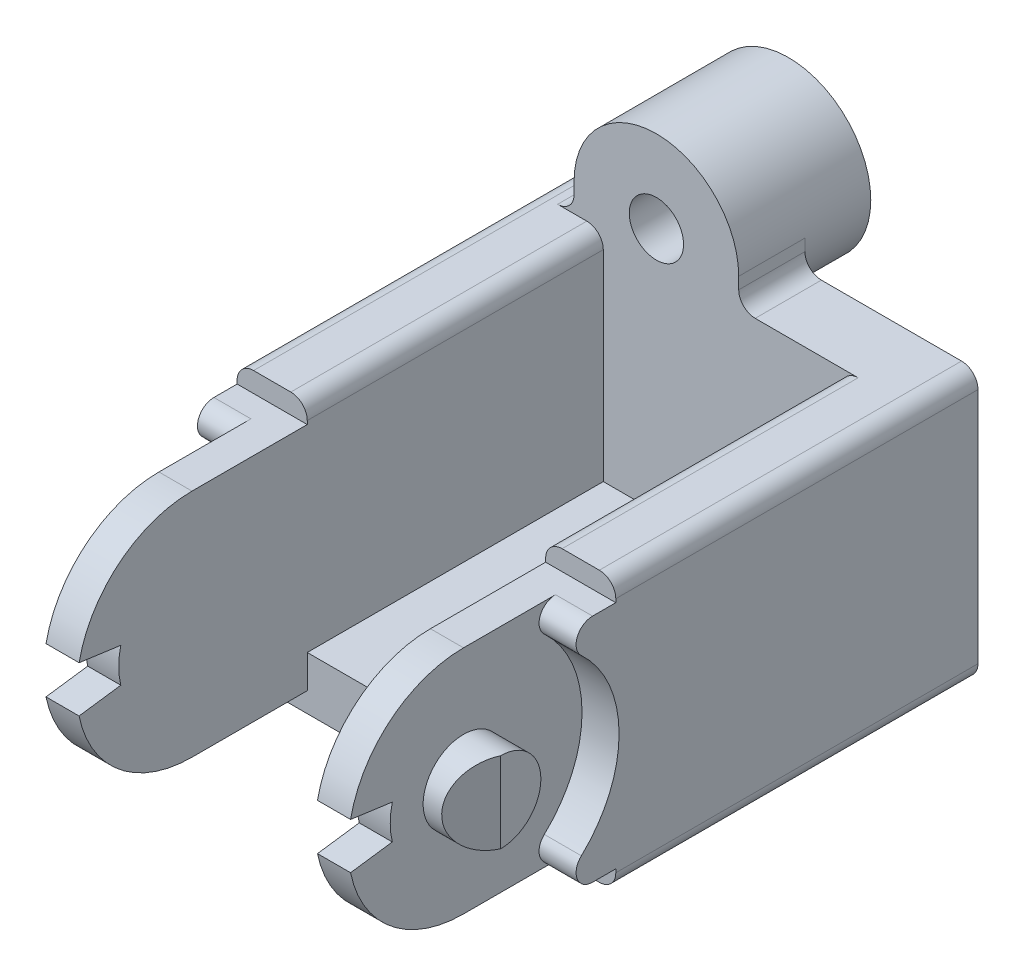
SolidWorks part; units mm, degrees
ref_plane "Front Plane" through (0, 0, 0) normal (0, 0, 1) x (1, 0, 0)
ref_plane "Top Plane" through (0, 0, 0) normal (0, 1, 0) x (1, 0, 0)
ref_plane "Right Plane" through (0, 0, 0) normal (1, 0, 0) x (0, 0, -1)
sketch "Sketch1" plane through (0, 0, 0) normal (0, 0, 1) x (1, 0, 0)
  line L0 (6, -1.7119) -> (14.5132, -1.7119)
  line L1 (-6.4868, -1.7119) -> (-6, -1.7119)
  line L2 (14.5132, -18.1319) -> (-6.4868, -18.1319)
  line L15 (15.5132, -2.7119) -> (15.5132, -17.1319)
  line L16 (-7.4868, -2.7119) -> (-7.4868, -17.1319)
  line L18 (-5, 0) -> (-5, -0.7119)
  line L20 (5, 0) -> (5, -0.7119)
  circle A3 centre (0, 0) radius 1.65
  arc A4 (14.5132, -18.1319) -> (15.5132, -17.1319) centre (14.5132, -17.1319) ccw
  arc A5 (14.5132, -1.7119) -> (15.5132, -2.7119) centre (14.5132, -2.7119) cw
  arc A6 (-6.4868, -1.7119) -> (-7.4868, -2.7119) centre (-6.4868, -2.7119) ccw
  arc A7 (-6.4868, -18.1319) -> (-7.4868, -17.1319) centre (-6.4868, -17.1319) cw
  arc A9 (5, 0) -> (-5, 0) centre (0, 0) ccw
  arc A10 (6, -1.7119) -> (5, -0.7119) centre (6, -0.7119) cw
  arc A11 (-5, -0.7119) -> (-6, -1.7119) centre (-6, -0.7119) cw
  point P39 (0, 0)
extrude "Boss-Extrude1" add sketch "Sketch1" along normal blind 40
sketch "Sketch2" plane through (0, 0, 40) normal (0, 0, 1) x (1, 0, 0)
  line L0 (5, 0) -> (5, -0.7119)
  line L2 (-5, -0.7119) -> (-5, 0)
  line L3 (-3.2268, -14.9119) -> (-3.2268, -2.7119)
  line L4 (-4.2268, -1.7119) -> (-6, -1.7119)
  line L5 (-3.2268, -14.9119) -> (11.2532, -14.9119)
  line L6 (11.2532, -14.9119) -> (11.2532, -2.7119)
  line L9 (12.2532, -1.7119) -> (6, -1.7119)
  arc A1 (-6, -1.7119) -> (-5, -0.7119) centre (-6, -0.7119) ccw
  arc A2 (5, -0.7119) -> (6, -1.7119) centre (6, -0.7119) ccw
  arc A3 (11.2532, -2.7119) -> (12.2532, -1.7119) centre (12.2532, -2.7119) cw
  arc A4 (-3.2268, -2.7119) -> (-4.2268, -1.7119) centre (-4.2268, -2.7119) ccw
  arc A5 (5, 0) -> (-5, 0) centre (0, 0) ccw
extrude "Cut-Extrude1" cut sketch "Sketch2" against normal offset from surface (31.98 mm away) 8.02 up to face at (2.2932, -5.6884, 0)
sketch "Sketch3" plane through (0, 0, 0) normal (0, 0, -1) x (-1, 0, 0)
  line L0 (-5, 0) -> (-5, -0.7119)
  line L2 (5, 0) -> (5, -0.7119)
  line L3 (-14.5132, -1.7119) -> (-6, -1.7119)
  line L4 (-15.5132, -2.7119) -> (-15.5132, -17.1319)
  line L6 (-14.5132, -18.1319) -> (6.4868, -18.1319)
  line L8 (7.4868, -17.1319) -> (7.4868, -2.7119)
  line L10 (6.4868, -1.7119) -> (6, -1.7119)
  arc A0 (-5, 0) -> (5, 0) centre (0, 0) ccw
  arc A1 (5, -0.7119) -> (6, -1.7119) centre (6, -0.7119) ccw
  arc A2 (-6, -1.7119) -> (-5, -0.7119) centre (-6, -0.7119) ccw
  arc A3 (7.4868, -2.7119) -> (6.4868, -1.7119) centre (6.4868, -2.7119) ccw
  arc A4 (-14.5132, -1.7119) -> (-15.5132, -2.7119) centre (-14.5132, -2.7119) ccw
  arc A5 (-15.5132, -17.1319) -> (-14.5132, -18.1319) centre (-14.5132, -17.1319) ccw
  arc A6 (6.4868, -18.1319) -> (7.4868, -17.1319) centre (6.4868, -17.1319) ccw
  circle A7 centre (0, 0) radius 3.3
extrude "Cut-Extrude2" cut sketch "Sketch3" against normal blind 4
sketch "Sketch4" plane through (0, 0, 40) normal (0, 0, 1) x (1, 0, 0)
  line L1 (-3.2268, -16.9219) -> (-3.2268, -2.9219)
  line L3 (11.2532, -16.9219) -> (11.2532, -2.9219)
  line L5 (-7.4868, -1.7119) -> (15.5132, -1.7119)
  line L6 (-7.4868, -1.7119) -> (-7.4868, -2.9219)
  line L7 (-7.4868, -2.9219) -> (-3.2268, -2.9219)
  line L8 (15.5132, -1.7119) -> (15.5132, -2.9219)
  line L9 (11.2532, -2.9219) -> (15.5132, -2.9219)
  line L10 (-7.4868, -18.1319) -> (15.5132, -18.1319)
  line L11 (-7.4868, -18.1319) -> (-7.4868, -16.9219)
  line L12 (-7.4868, -16.9219) -> (-3.2268, -16.9219)
  line L13 (15.5132, -18.1319) -> (15.5132, -16.9219)
  line L14 (11.2532, -16.9219) -> (15.5132, -16.9219)
extrude "Cut-Extrude3" cut sketch "Sketch4" against normal blind 14
sketch "Sketch5" plane through (15.5132, 0, 0) normal (1, 0, 0) x (0, 0, -1)
  line L0 (-39.8586, -8.5219) -> (-37.3243, -8.8719)
  line L1 (-39.8586, -11.3219) -> (-37.3243, -10.9719)
  line L2 (-33, -2.9219) -> (-40, -2.9219)
  line L3 (-40, -2.9219) -> (-40, -16.9219)
  line L4 (-40, -16.9219) -> (-33, -16.9219)
  arc A0 (-39.8586, -11.3219) -> (-33, -16.9219) centre (-33, -9.9219) ccw
  arc A1 (-37.3243, -8.8719) -> (-37.3243, -10.9719) centre (-33, -9.9219) ccw
  arc A2 (-33, -2.9219) -> (-39.8586, -8.5219) centre (-33, -9.9219) ccw
extrude "Cut-Extrude4" cut sketch "Sketch5" against normal up to surface (23 mm away) up to face at (-7.4868, -9.9219, 24)
sketch "Sketch6" plane through (15.5132, 0, 0) normal (1, 0, 0) x (0, 0, -1)
  line L0 (-27.4107, -2.9219) -> (-31.3148, -2.9219)
  line L1 (-27.4107, -16.9219) -> (-31.3148, -16.9219)
  circle A0 centre (-33, -9.9219) radius 2.45
  arc A1 (-27.4107, -16.9219) -> (-28.0923, -15.1902) centre (-27.4107, -15.9219) cw
  arc A2 (-27.4107, -2.9219) -> (-28.0923, -4.6536) centre (-27.4107, -3.9219) ccw
  arc A3 (-31.3148, -2.9219) -> (-31.3148, -16.9219) centre (-33, -9.9219) ccw
  arc A4 (-28.0923, -15.1902) -> (-28.0923, -4.6536) centre (-33, -9.9219) ccw
extrude "Cut-Extrude5" cut sketch "Sketch6" against normal blind 2.25
extrude "Cut-Extrude6" cut sketch "Sketch6<2>" along normal blind 2.25 from surface starting at face at (-7.4868, -9.9219, 27.8739)
sketch "Sketch6<2>" plane through (15.5132, 0, 0) normal (1, 0, 0) x (0, 0, -1) same geometry as "Sketch6"
sketch "Sketch7" plane through (0, -2.9219, 0) normal (0, 1, 0) x (1, 0, 0)
  line L0 (-7.4868, -33) -> (-6.3618, -35.45)
  line L1 (-6.3618, -35.45) -> (-7.4868, -35.45)
  line L2 (-7.4868, -35.45) -> (-7.4868, -33)
  line L3 (15.5132, -33) -> (15.5132, -35.45)
  line L4 (15.5132, -35.45) -> (14.3882, -35.45)
  line L5 (14.3882, -35.45) -> (15.5132, -33)
extrude "Cut-Extrude7" cut sketch "Sketch7" against normal up to surface (14 mm away) up to face at (13.3432, -16.9219, 28.8036)
